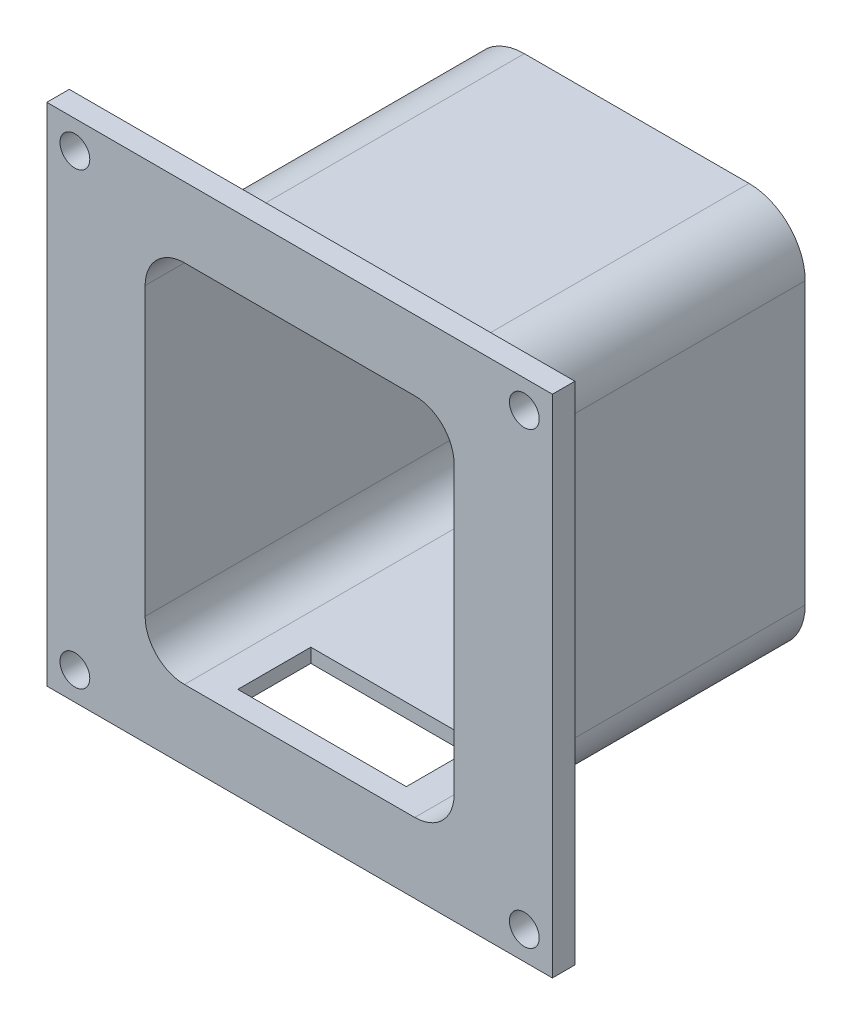
SolidWorks part; units mm, degrees
ref_plane "Front Plane" through (0, 0, 0) normal (0, 0, 1) x (1, 0, 0)
ref_plane "Top Plane" through (0, 0, 0) normal (0, 1, 0) x (1, 0, 0)
ref_plane "Right Plane" through (0, 0, 0) normal (1, 0, 0) x (0, 0, -1)
sketch "Sketch1" plane through (0, 0, 0) normal (0, 0, 1) x (1, 0, 0)
  line L1 (-30, -35) -> (30, -35)
  line L2 (-30, -35) -> (-30, 35)
  line L3 (-30, 35) -> (30, 35)
  line L4 (30, -35) -> (30, 35)
  line L5 (-30, -35) -> (30, 35) construction
  line L6 (-30, 35) -> (30, -35) construction
  line L7 (20.5, -32.5) -> (-20.5, -32.5)
  line L8 (27.5, -25.5) -> (27.5, 25.5)
  line L9 (20.5, 32.5) -> (-20.5, 32.5)
  line L10 (-27.5, -25.5) -> (-27.5, 25.5)
  line L11 (27.5, -32.5) -> (-27.5, 32.5) construction
  line L12 (27.5, 32.5) -> (-27.5, -32.5) construction
  arc A0 (-20.5, -32.5) -> (-27.5, -25.5) centre (-20.5, -25.5) cw
  arc A1 (20.5, -32.5) -> (27.5, -25.5) centre (20.5, -25.5) ccw
  arc A2 (27.5, 25.5) -> (20.5, 32.5) centre (20.5, 25.5) ccw
  arc A3 (-20.5, 32.5) -> (-27.5, 25.5) centre (-20.5, 25.5) ccw
  point P0 (0, 0)
  point P6 (0, 0)
  dimension "D3" = 7
  dimension "D1" = 70
  dimension "D2" = 60
  dimension "D4" = 65
  dimension "D5" = 55
extrude "Boss-Extrude1" add sketch "Sketch1" along normal blind 60
sketch "Sketch2" plane through (0, 0, 0) normal (0, 0, -1) x (-1, 0, 0)
  line L0 (0, 0.5) -> (0, -32.5) construction
  line L1 (-17.65, -4.5) -> (-10.65, -4.5)
  line L2 (-10.65, -4.5) -> (-10.65, -27.5)
  line L3 (-10.65, -27.5) -> (10.65, -27.5)
  line L4 (10.65, -27.5) -> (10.65, -4.5)
  line L5 (10.65, -4.5) -> (17.65, -4.5)
  line L6 (17.65, -4.5) -> (17.65, -25.5)
  line L7 (-17.65, -4.5) -> (-17.65, -25.5)
  line L8 (0, 0.5) -> (13.5, 0.5) construction
  line L9 (13.5, 0.5) -> (13.5, -8.5) construction
  line L10 (13.5, -8.5) -> (13.5, -16.5) construction
  line L11 (13.5, -16.5) -> (13.5, -24.5) construction
  line L12 (-20.5, -32.5) -> (20.5, -32.5)
  line L13 (-17.65, -25.5) -> (-27.5, -25.5)
  line L14 (17.65, -25.5) -> (27.5, -25.5)
  line L15 (20.5, -32.5) -> (-20.5, -32.5) construction
  line L16 (30, -35) -> (-30, -35) construction
  circle A0 centre (0, 0.5) radius 11 construction
  circle A1 centre (13.5, -8.5) radius 1.25
  arc A2 (-27.5, -25.5) -> (-20.5, -32.5) centre (-20.5, -25.5) ccw
  circle A3 centre (13.5, -16.5) radius 1.25
  circle A4 centre (13.5, -24.5) radius 1.25
  circle A5 centre (-13.5, -8.5) radius 1.25
  circle A6 centre (-13.5, -16.5) radius 1.25
  circle A7 centre (-13.5, -24.5) radius 1.25
  arc A8 (20.5, -32.5) -> (27.5, -25.5) centre (20.5, -25.5) ccw
  arc A9 (-27.5, -25.5) -> (-20.5, -32.5) centre (-20.5, -25.5) ccw construction
  point P6 (0, -27.5)
  point P34 (0, -32.5)
  dimension "D1" = 22
  dimension "D5" = 2.5
  dimension "D2" = 21.3
  dimension "D3" = 13.5
  dimension "D4" = 9
  dimension "D6" = 8
  dimension "D7" = 8
  dimension "D8" = 7
  dimension "D9" = 5
  dimension "D10" = 5
  dimension "D11" = 35.5
extrude "Boss-Extrude2" add sketch "Sketch2" against normal blind 4
sketch "Sketch4" plane through (0, -35, 0) normal (0, -1, 0) x (1, 0, 0)
  line L0 (-30, 60) -> (30, 60) construction
  line L1 (15, 60) -> (-15, 60)
  line L2 (15, 60) -> (15, 43)
  line L3 (15, 43) -> (-15, 43)
  line L4 (-15, 60) -> (-15, 43)
  line L5 (0, 0) -> (0, 60) construction
  line L6 (-30, 0) -> (30, 0) construction
  point P10 (0, 60)
  dimension "D1" = 30
  dimension "D2" = 17
extrude "Cut-Extrude1" cut sketch "Sketch4" against normal up to surface (2.5 mm away) up to face at (0, -32.5, 32)
sketch "Sketch5" plane through (0, 0, 0) normal (0, 0, -1) x (-1, 0, 0)
  circle A0 centre (-13.5, -8.5) radius 2.25
  circle A1 centre (-13.5, -16.5) radius 2.25
  circle A2 centre (-13.5, -24.5) radius 2.25
  circle A3 centre (13.5, -24.5) radius 2.25
  circle A4 centre (13.5, -16.5) radius 2.25
  circle A5 centre (13.5, -8.5) radius 2.25
  dimension "D1" = 4.5
extrude "Cut-Extrude2" cut sketch "Sketch5" against normal blind 2.5
sketch "Sketch6" plane through (0, 0, 60) normal (0, 0, 1) x (1, 0, 0)
  line L1 (-45, 45) -> (45, 45)
  line L2 (-45, 45) -> (-45, -45)
  line L3 (-45, -45) -> (45, -45)
  line L4 (45, 45) -> (45, -45)
  line L5 (-45, 45) -> (45, -45) construction
  line L6 (-45, -45) -> (45, 45) construction
  line L7 (40, 40) -> (-40, 40) construction
  line L8 (40, 40) -> (40, -40) construction
  line L9 (40, -40) -> (-40, -40) construction
  line L10 (-40, 40) -> (-40, -40) construction
  line L11 (40, 40) -> (-40, -40) construction
  line L12 (40, -40) -> (-40, 40) construction
  circle A0 centre (40, 40) radius 2.65
  circle A1 centre (-40, 40) radius 2.65
  circle A2 centre (-40, -40) radius 2.65
  circle A3 centre (40, -40) radius 2.65
  point P0 (0, 0)
  point P6 (0, 0)
  dimension "D5" = 5.3
  dimension "D1" = 90
  dimension "D2" = 90
  dimension "D3" = 80
  dimension "D4" = 80
extrude "Boss-Extrude3" add sketch "Sketch6" against normal blind 4
fillet "Fillet1" radius 10 4 edges at (-30, -35, 28) (30, -35, 28) (-30, 35, 28) (30, 35, 28)
sketch "Sketch8" plane through (0, 0, 56) normal (0, 0, -1) x (-1, 0, 0)
  line L0 (-20.5, 32.5) -> (20.5, 32.5) construction
  line L1 (-20.5, 32.5) -> (20.5, 32.5)
  line L2 (27.5, 25.5) -> (27.5, -25.5) construction
  line L3 (27.5, 25.5) -> (27.5, -25.5)
  line L4 (-27.5, -25.5) -> (-27.5, 25.5) construction
  line L5 (-27.5, -25.5) -> (-27.5, 25.5)
  line L6 (-20.5, -32.5) -> (20.5, -32.5)
  arc A0 (-20.5, 32.5) -> (-27.5, 25.5) centre (-20.5, 25.5) ccw construction
  arc A1 (-20.5, 32.5) -> (-27.5, 25.5) centre (-20.5, 25.5) ccw
  arc A2 (27.5, 25.5) -> (20.5, 32.5) centre (20.5, 25.5) ccw construction
  arc A3 (27.5, 25.5) -> (20.5, 32.5) centre (20.5, 25.5) ccw
  arc A4 (20.5, -32.5) -> (27.5, -25.5) centre (20.5, -25.5) ccw construction
  arc A5 (20.5, -32.5) -> (27.5, -25.5) centre (20.5, -25.5) ccw
  arc A6 (-27.5, -25.5) -> (-20.5, -32.5) centre (-20.5, -25.5) ccw construction
  arc A7 (-27.5, -25.5) -> (-20.5, -32.5) centre (-20.5, -25.5) ccw
extrude "Cut-Extrude5" cut sketch "Sketch8" against normal through all
fillet "Fillet3" radius 5 2 edges at (-17.65, -25.5, 2) (17.65, -25.5, 2)
fillet "Fillet4" radius 5 2 edges at (-27.5, -25.5, 2) (27.5, -25.5, 2)
